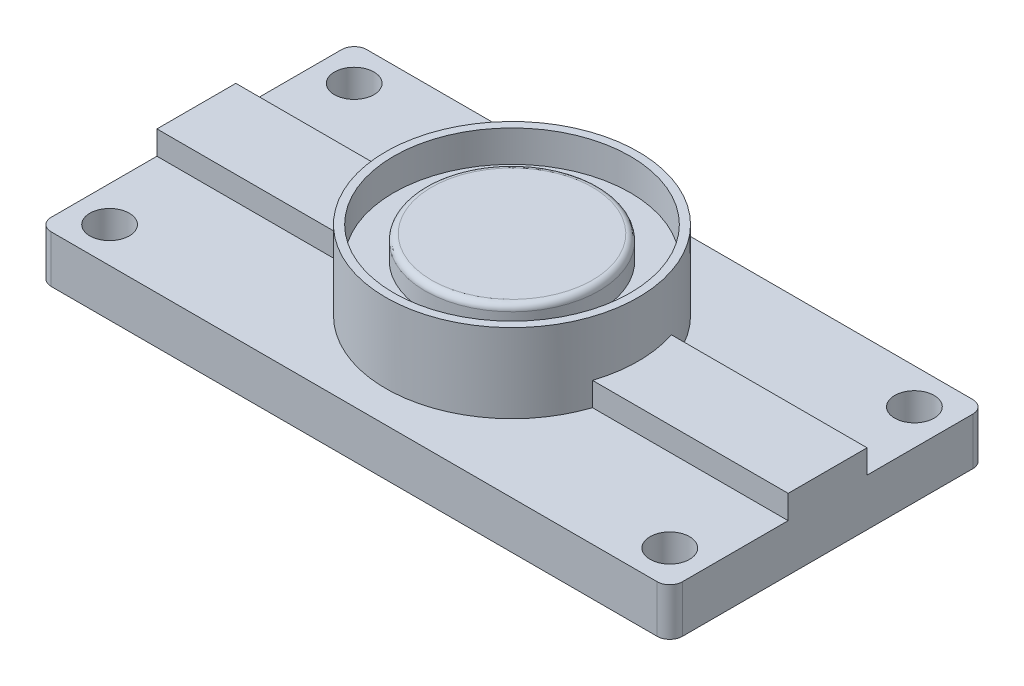
SolidWorks part; units mm, degrees
note: The reader was unsure of these and kept them because the rebuilt part matched: shared geometry of "Sketch1<5>", "Sketch1<6>", "Sketch4<2>".
ref_plane "Front Plane" through (0, 0, 0) normal (0, 0, 1) x (1, 0, 0)
ref_plane "Top Plane" through (0, 0, 0) normal (0, 1, 0) x (1, 0, 0)
ref_plane "Right Plane" through (0, 0, 0) normal (1, 0, 0) x (0, 0, -1)
sketch "Sketch1" plane through (0, 0, 0) normal (0, 1, 0) x (1, 0, 0)
  line L0 (-55, 0) -> (55, 0) construction
  line L1 (-20, 10) -> (20, 10)
  line L2 (-20, 10) -> (-20, -10)
  line L3 (-20, -10) -> (20, -10)
  line L4 (20, 10) -> (20, -10)
  line L5 (0, -55) -> (0, 55) construction
  line L7 (-20, 2.5) -> (20, 2.5)
  line L8 (-20, 2.5) -> (-20, -2.5)
  line L9 (-20, -2.5) -> (20, -2.5)
  line L10 (20, 2.5) -> (20, -2.5)
  circle A0 centre (0, 0) radius 8
  circle A1 centre (-17.75, 7.75) radius 1.25
  circle A2 centre (-17.75, -7.75) radius 1.25
  circle A3 centre (17.75, -7.75) radius 1.25
  circle A4 centre (17.75, 7.75) radius 1.25
  point P4 (-20, 0)
  point P6 (0, -10)
  dimension "D3" = 16
  dimension "D4" = 2.5
  dimension "D1" = 40
  dimension "D2" = 20
  dimension "D5" = 2.25
  dimension "D6" = 2.25
  dimension "D7" = 5
  dimension "D8" = 7.5
extrude "Boss-Extrude1" add sketch "Sketch1" along normal blind 3 contours A0 | L2 L1 L4 L3 | A3 | A4 | A2 | A1
extrude "Boss-Extrude3" add sketch "Sketch1<5>" along normal blind 8 contours A0 | L9 A0 | L7 A0
sketch "Sketch1<5>" plane through (0, 0, 0) normal (0, 1, 0) x (1, 0, 0) same geometry as "Sketch1"
extrude "Boss-Extrude4" add sketch "Sketch1<6>" along normal blind 4.5 contours A0 L7 L2 L9 | A0 L9 L4 L7
sketch "Sketch1<6>" plane through (0, 0, 0) normal (0, 1, 0) x (1, 0, 0) same geometry as "Sketch1"
sketch "Sketch2" plane through (0, 0, 0) normal (0, -1, 0) x (1, 0, 0)
  line L0 (-10, 0) -> (10, 0) construction
  line L1 (-10, 8) -> (10, 8)
  line L2 (-10, -8) -> (10, -8)
  line L3 (-20, -10) -> (-20, 10) construction
  line L4 (20, -10) -> (20, 10) construction
  arc A0 (-10, 8) -> (-10, -8) centre (-10, 0) ccw
  arc A1 (10, -8) -> (10, 8) centre (10, 0) ccw
  point P3 (0, 0)
  point P8 (-10.7762, 0)
  point P9 (13.8798, 0)
  point P10 (10.6469, 0)
  dimension "D1" = 16
  dimension "D2" = 10
  dimension "D3" = 10
extrude "Cut-Extrude1" cut sketch "Sketch2" against normal blind 1
sketch "Sketch3" plane through (0, 1, 0) normal (0, -1, 0) x (1, 0, 0)
  line L0 (-10, 0) -> (10, 0) construction
  line L1 (-10, 7.5) -> (10, 7.5)
  line L2 (-10, -7.5) -> (10, -7.5)
  line L3 (10, 8) -> (-10, 8) construction
  line L4 (-20, -10) -> (-20, 10) construction
  line L5 (20, -10) -> (20, 10) construction
  line L6 (-10, 6.5) -> (10, 6.5)
  line L7 (-10, -6.5) -> (10, -6.5)
  circle A0 centre (0, 0) radius 4.8598
  circle A1 centre (0, 0) radius 4.04
  arc A2 (-10, 7.5) -> (-10, -7.5) centre (-10, 0) ccw
  arc A3 (10, -7.5) -> (10, 7.5) centre (10, 0) ccw
  arc A4 (10, -6.5) -> (10, 6.5) centre (10, 0) ccw
  arc A5 (-10, 6.5) -> (-10, -6.5) centre (-10, 0) ccw
  point P6 (0, 0)
  point P13 (-10.0003, 0)
  dimension "D4" = 9.7196
  dimension "D5" = 8.0799
  dimension "D1" = 0.5
  dimension "D2" = 10
  dimension "D3" = 10
  dimension "D6" = 1
extrude "Boss-Extrude5" add sketch "Sketch3" along normal blind 0.5 contours L2 A3 L1 A2 A5 L6 A4 L7 | A0 L0 A1 | L0 A0 A1
fillet "Fillet1" radius 0.2 15 edges at (0, 1, 6.5) (16.5, 1, 0) (0, 1, -6.5) (-16.5, 1, 0) (0, 1, -4.8598) (0, 0.5, -4.8598) (0, 0.5, -4.04) (-17.5, 0.5, 0) (0, 0.5, 7.5) (17.5, 0.5, 0) (0, 0.5, -7.5) (0, 0.5, -6.5) (16.5, 0.5, 0) (0, 0.5, 6.5) (-16.5, 0.5, 0)
fillet "Fillet2" radius 0.8 4 edges at (20, 1.5, 10) (20, 1.5, -10) (-20, 1.5, 10) (-20, 1.5, -10)
sketch "Sketch4" plane through (0, 8, 0) normal (0, 1, 0) x (1, 0, 0)
  circle A0 centre (0, 0) radius 7.5
  circle A1 centre (0, 0) radius 5.5
  dimension "D1" = 15
  dimension "D2" = 11
extrude "Cut-Extrude2" cut sketch "Sketch4" against normal blind 2
extrude "Cut-Extrude3" cut sketch "Sketch4<2>" against normal blind 0.5 contours A1
sketch "Sketch4<2>" plane through (0, 8, 0) normal (0, 1, 0) x (1, 0, 0) same geometry as "Sketch4"
fillet "Fillet3" radius 0.4 1 edges at (0, 7.5, 5.5)
